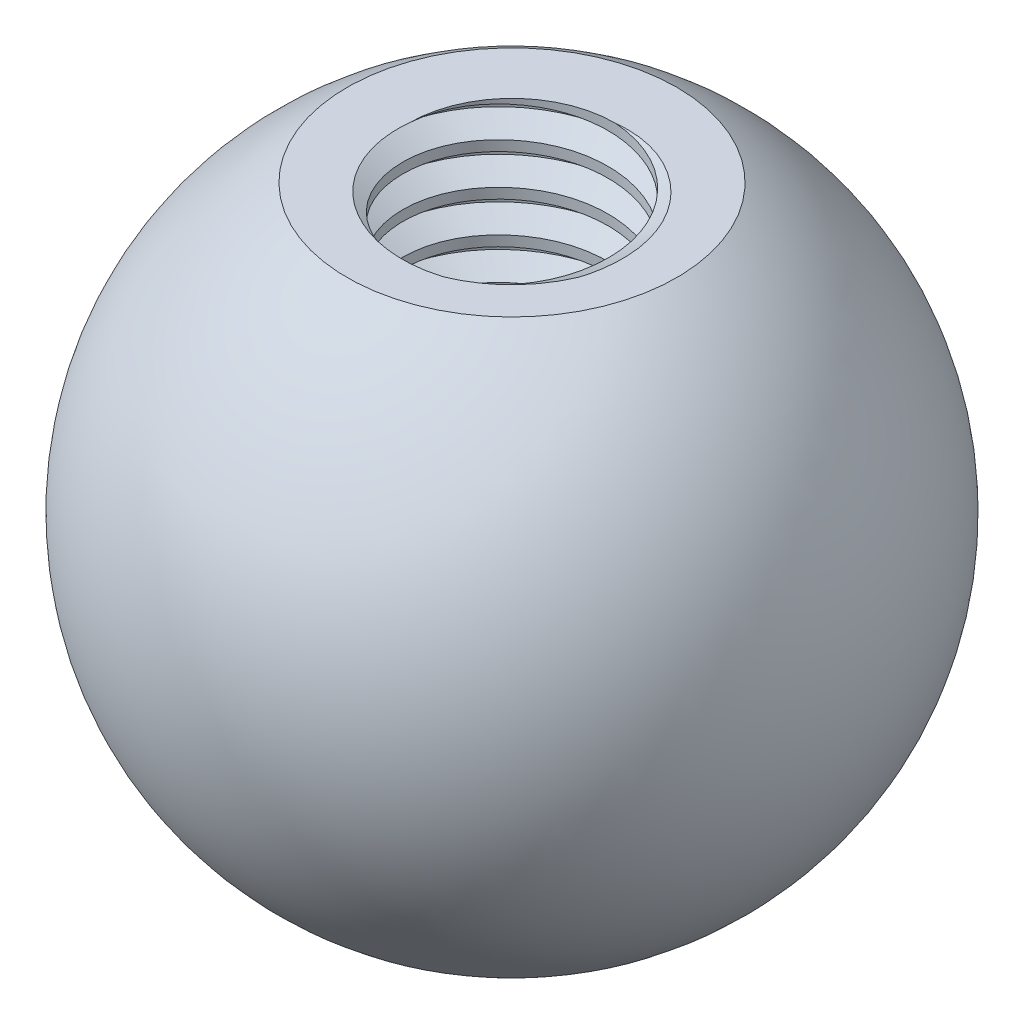
SolidWorks part; units mm, degrees
ref_plane "Front Plane" through (0, 0, 0) normal (0, 0, 1) x (1, 0, 0)
ref_plane "Top Plane" through (0, 0, 0) normal (0, 1, 0) x (1, 0, 0)
ref_plane "Right Plane" through (0, 0, 0) normal (1, 0, 0) x (0, 0, -1)
sketch "Sketch1" plane through (0, 0, 0) normal (1, 0, 0) x (0, 0, -1)
  line L0 (0, 0) -> (2, 0)
  line L1 (0, -7.4641) -> (0, 0)
  arc A0 (2, 0) -> (0, -7.4641) centre (0, -3.4641) cw
  point P5 (0, 0)
  point P6 (0, 0)
  dimension "D1" = 4
  dimension "D2" = 2
revolve "Revolve1" add sketch "Sketch1" angle 360 about L1
sketch "Sketch4" plane through (0, 0, 0) normal (0, 1, 0) x (1, 0, 0)
  point P0 (0, 0)
hole_wizard "Tap Drill for M3 Tap1" positions "Sketch4" profile "Sketch5" hole size "M3" standard "ISO"
sketch "Sketch5" plane through (0, 0, 0) normal (1, 0, 0) x (0, 0, 1)
  line L0 (0, 0) -> (0, 5.7511)
  line L1 (0, 5.7511) -> (1.25, 5)
  line L2 (1.25, 5) -> (1.25, 0)
  line L5 (1.25, 0) -> (0, 0)
  line L10 (0, 5.7511) -> (-1.25, 5) construction
  line L11 (0, -6.35) -> (0, 107.95) construction
  dimension "Hole Dia." = 2.5
  dimension "Hole Depth" = 5
  dimension "Drill Angle" = 118
thread "Thread1" pitch 0.5 method cut profile "Thread Profile1" start angle 0, offset 0.5, length 0, pitch 0.5, diameter 2.5
ref_plane "Plane1" through (-1.25, 0.5, 0) normal (0, 0, 1) x (-1, 0, 0)
sketch "Thread Profile1" plane through (-1.25, 0.5, 0) normal (0, 0, 1) x (-1, 0, 0)
  line L0 (0, 0) -> (0, 0.5) construction
  line L1 (0, 0) -> (0.2706, 0.1562)
  line L2 (0.2706, 0.1562) -> (0.2706, 0.2187)
  line L3 (0.2706, 0.2187) -> (0, 0.375)
  line L4 (0.2706, 0.1875) -> (0, 0.1875) construction
  line L11 (0, 0) -> (0, 0.375)
  point P2 (0, 0)
  dimension "Pitch" = 0.5
  dimension "Profile_Angle" = 60
  dimension "Profile_Land" = 0.0625
  dimension "Profile_Height" = 0.2706
